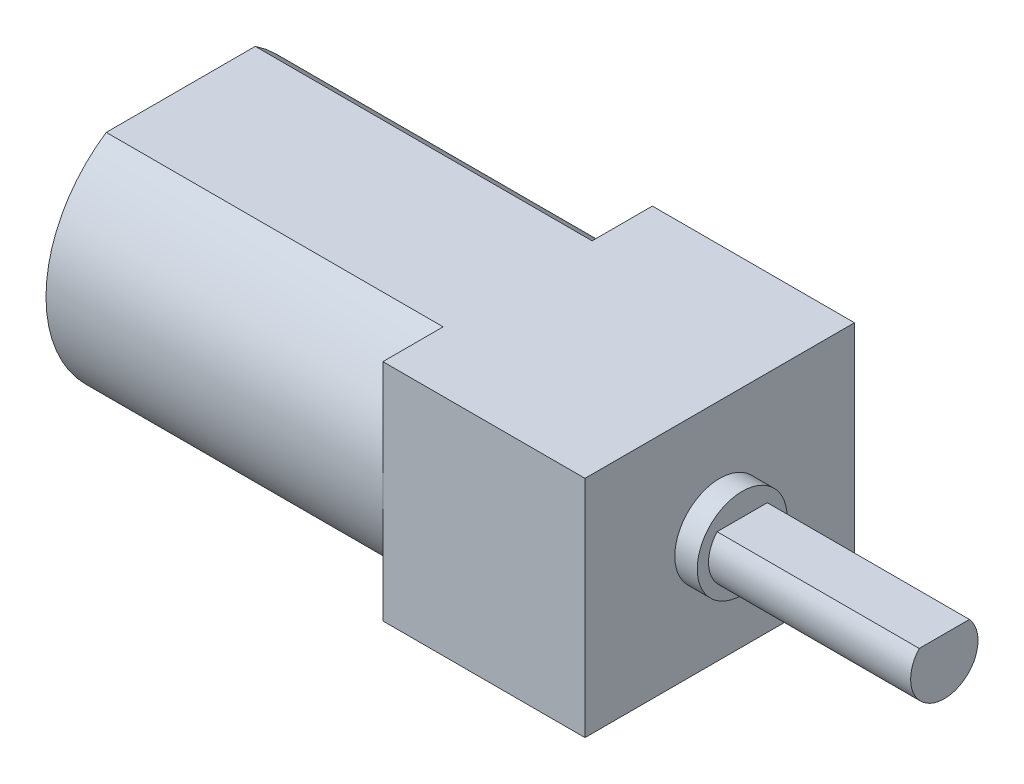
SolidWorks part; units mm, degrees
ref_plane "Front" through (0, 0, 0) normal (0, 0, 1) x (1, 0, 0)
ref_plane "Top" through (0, 0, 0) normal (0, 1, 0) x (1, 0, 0)
ref_plane "Right" through (0, 0, 0) normal (1, 0, 0) x (0, 0, -1)
sketch "Эскиз1" plane through (0, 0, 0) normal (0, 1, 0) x (1, 0, 0)
  line L1 (-12, 6) -> (12, 6)
  line L2 (-12, 6) -> (-12, -6)
  line L3 (-12, -6) -> (12, -6)
  line L4 (12, 6) -> (12, -6)
  line L5 (-12, 6) -> (12, -6) construction
  line L6 (-12, -6) -> (12, 6) construction
  point P0 (0, 0)
  dimension "D1" = 12
  dimension "D2" = 24
extrude "Бобышка-Вытянуть1" add sketch "Эскиз1" along normal mid plane 10
sketch "Эскиз2" plane through (-12, 0, 0) normal (-1, 0, 0) x (0, 0, 1)
  circle A0 centre (0, 0) radius 2.5
  circle A1 centre (0, 0) radius 6
  line M1 (-6, -5) -> (6, -5)
  line M2 (6, -5) -> (6, 5)
  line M3 (6, 5) -> (-6, 5)
  line M4 (-6, 5) -> (-6, -5)
  dimension "D1" = 5
  dimension "D2" = 12
extrude "Вырез-Вытянуть1" cut sketch "Эскиз2" against normal blind 15 contours A1 M3 M4 | A1 M4 M1 | A1 M2 M3 | A1 M1 M2 region at (-12, -3.8127, 5.2392) region at (-12, 3.8127, 5.2392) region at (-12, 3.8127, -5.2392) region at (-12, -3.8127, -5.2392)
extrude "Бобышка-Вытянуть2" add sketch "Эскиз2<3>" along normal blind 1.5 contours A0 region at (-12, 0, 0)
sketch "Эскиз2<3>" plane through (-12, 0, 0) normal (-1, 0, 0) x (0, 0, 1) same geometry as "Эскиз2"
sketch "Эскиз4" plane through (12, 0, 0) normal (1, 0, 0) x (0, 0, -1)
  circle A0 centre (0, 0) radius 2
  dimension "D1" = 4
extrude "Бобышка-Вытянуть3" add sketch "Эскиз4" along normal blind 1
sketch "Эскиз5" plane through (13, 0, 0) normal (1, 0, 0) x (0, 0, -1)
  line L0 (-1.118, 1) -> (1.118, 1)
  circle A0 centre (0, 0) radius 1.5
  dimension "D1" = 3
  dimension "D2" = 1
extrude "Бобышка-Вытянуть4" add sketch "Эскиз5" along normal blind 9 contours L0 A0 region at (13, -0.148, 0)
